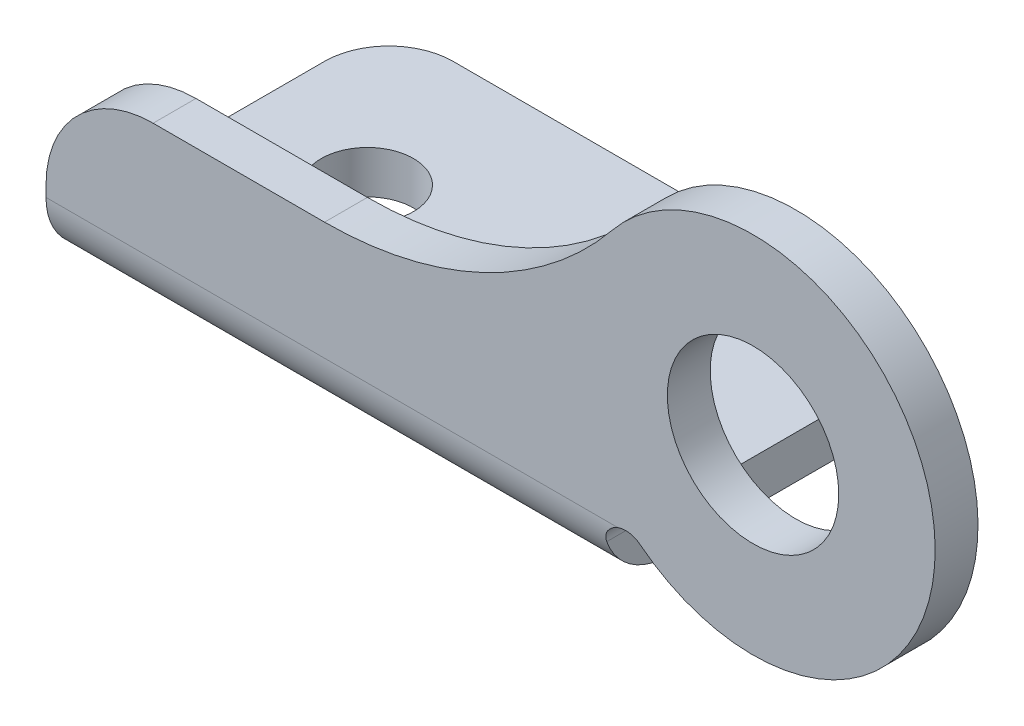
SolidWorks part; units mm, degrees
ref_plane "前视基准面" through (0, 0, 0) normal (0, 0, 1) x (1, 0, 0)
ref_plane "上视基准面" through (0, 0, 0) normal (0, 1, 0) x (1, 0, 0)
ref_plane "右视基准面" through (0, 0, 0) normal (1, 0, 0) x (0, 0, -1)
sketch "草图1" plane through (0, 0, 0) normal (0, 1, 0) x (1, 0, 0)
  line L1 (13, -8) -> (-13, -8)
  line L2 (13, -8) -> (13, 8)
  line L3 (13, 8) -> (-13, 8)
  line L4 (-13, -8) -> (-13, 8)
  line L5 (13, -8) -> (-13, 8) construction
  line L6 (13, 8) -> (-13, -8) construction
  point P0 (0, 0)
  dimension "D1" = 26
  dimension "D2" = 16
extrude "凸台-拉伸1" add sketch "草图1" along normal blind 2
sketch "草图3" plane through (0, 0, 8) normal (0, 0, 1) x (1, 0, 0)
  line L0 (-13, 2) -> (-13, 8.5)
  line L1 (-13, 8.5) -> (0, 8.5)
  line L2 (-13, 0) -> (13, 0) construction
  line L3 (-13, 2) -> (-13, 0) construction
  line L4 (13, 2) -> (13, 0) construction
  line L5 (13, 2) -> (-13, 2)
  arc A0 (0, 8.5) -> (13.4115, 14.8705) centre (0, 25.8026) ccw
  arc A1 (13.4115, 14.8705) -> (14.7251, 2.8347) centre (20, 9.5) cw
  arc A2 (14.7251, 2.8347) -> (13, 2) centre (14.0645, 2) ccw
  dimension "D1" = 9.5
  dimension "D3" = 8.5
  dimension "D2" = 33
  dimension "D4" = 8.5
extrude "凸台-拉伸2" add sketch "草图3" against normal blind 2
fillet "圆角1" radius 5 1 edges at (-13, 8.5, 7)
fillet "圆角2" radius 3 2 edges at (13, 1, -8) (-13, 1, -8)
sketch "草图4" plane through (0, 0, 8) normal (0, 0, 1) x (1, 0, 0)
  circle A0 centre (20, 9.5) radius 4
  dimension "D1" = 8
extrude "切除-拉伸1" cut sketch "草图4" against normal through all
sketch "草图5" plane through (0, 2, 0) normal (0, 1, 0) x (1, 0, 0)
  line L0 (10, 8) -> (-10, 8) construction
  line L1 (6, 1) -> (-7, 1) construction
  line L2 (-13, 5) -> (-13, -6) construction
  circle A0 centre (-7, 1) radius 2.15
  circle A1 centre (6, 1) radius 2.15
  dimension "D1" = 7
  dimension "D2" = 4.3
  dimension "D3" = 13
  dimension "D4" = 19
extrude "切除-拉伸2" cut sketch "草图5" against normal through all
fillet "圆角3" radius 3 1 edges at (0, 0, 8)
fillet "圆角4" radius 1 1 edges at (0, 2, 6)
